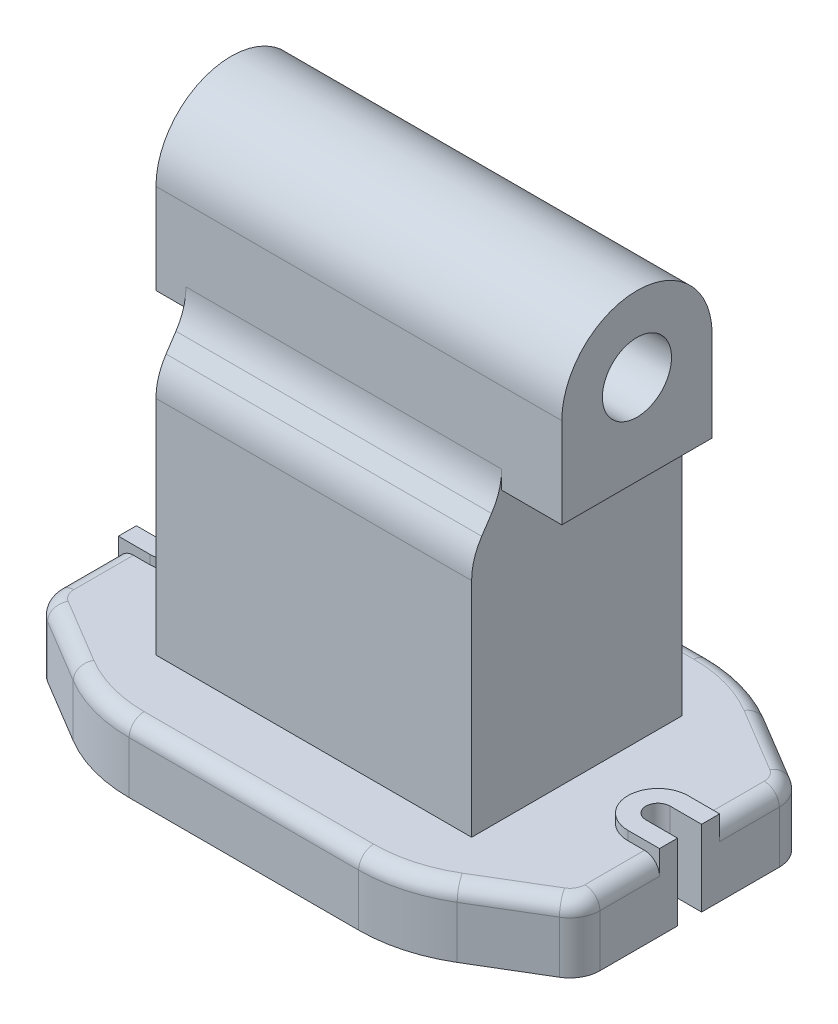
SolidWorks part; units mm, degrees
ref_plane "Front Plane" through (0, 0, 0) normal (0, 0, 1) x (1, 0, 0)
ref_plane "Top Plane" through (0, 0, 0) normal (0, 1, 0) x (1, 0, 0)
ref_plane "Right Plane" through (0, 0, 0) normal (1, 0, 0) x (0, 0, -1)
sketch "Sketch1" plane through (0, 0, 0) normal (0, 1, 0) x (1, 0, 0)
  line L0 (-27.5, 54.25) -> (-38, 54.25)
  line L1 (0, 0) -> (104, 0)
  line L3 (0, 116.5) -> (104, 116.5)
  line L5 (-38, 22.75) -> (0, 0)
  line L6 (-38, 54.25) -> (-38, 22.75)
  line L7 (-27.5, 62.25) -> (-38, 62.25)
  line L8 (-38, 62.25) -> (-38, 93.75)
  line L9 (-38, 93.75) -> (0, 116.5)
  line L10 (-38, 54.25) -> (-38, 62.25) construction
  line L11 (-38, 58.25) -> (142, 58.25) construction
  line L12 (52, 116.5) -> (52, 0) construction
  line L13 (142, 54.25) -> (142, 22.75)
  line L14 (142, 22.75) -> (104, 0)
  line L15 (131.5, 54.25) -> (142, 54.25)
  line L16 (131.5, 62.25) -> (142, 62.25)
  line L17 (142, 62.25) -> (142, 93.75)
  line L18 (142, 93.75) -> (104, 116.5)
  line L19 (142, 54.25) -> (142, 62.25) construction
  arc A0 (-27.5, 54.25) -> (-27.5, 62.25) centre (-27.5, 58.25) ccw
  arc A1 (131.5, 54.25) -> (131.5, 62.25) centre (131.5, 58.25) cw
  point P23 (144.2285, 58.25)
  point P24 (142, 58.25)
  dimension "D3" = 4
  dimension "D1" = 71
  dimension "D2" = 116.5
  dimension "D4" = 180
  dimension "D5" = 104
  dimension "D6" = 10.5
extrude "Base" add sketch "Sketch1" along normal blind 22.3
sketch "Sketch3" plane through (0, 22.3, 0) normal (0, 1, 0) x (1, 0, 0)
  line L0 (-27.5, 54.25) -> (-38, 54.25) construction
  line L1 (-38, 62.25) -> (-27.5, 62.25) construction
  line L2 (-27.5, 54.25) -> (-38, 54.25)
  line L3 (-38, 62.25) -> (-27.5, 62.25)
  line L8 (52, 0) -> (52, 116.5) construction
  line L9 (0, 0) -> (104, 0) construction
  line L10 (104, 116.5) -> (0, 116.5) construction
  line L11 (-38, 68.25) -> (-27.5, 68.25)
  line L12 (-27.5, 48.25) -> (-38, 48.25)
  line L13 (-38, 68.25) -> (-38, 62.25)
  line L14 (-38, 54.25) -> (-38, 48.25)
  line L15 (142, 54.25) -> (142, 48.25)
  line L16 (142, 68.25) -> (142, 62.25)
  line L17 (131.5, 48.25) -> (142, 48.25)
  line L18 (142, 68.25) -> (131.5, 68.25)
  line L19 (142, 62.25) -> (131.5, 62.25)
  line L20 (131.5, 54.25) -> (142, 54.25)
  arc A0 (-27.5, 54.25) -> (-27.5, 62.25) centre (-27.5, 58.25) ccw construction
  arc A1 (-27.5, 54.25) -> (-27.5, 62.25) centre (-27.5, 58.25) ccw
  arc A3 (-27.5, 48.25) -> (-27.5, 68.25) centre (-27.5, 58.25) ccw
  arc A4 (131.5, 48.25) -> (131.5, 68.25) centre (131.5, 58.25) cw
  arc A5 (131.5, 54.25) -> (131.5, 62.25) centre (131.5, 58.25) cw
  dimension "D1" = 6
extrude "Resalto - Furos de Fixação" add sketch "Sketch3" along normal blind 3
sketch "Sketch4" plane through (0, 22.3, 0) normal (0, 1, 0) x (1, 0, 0)
  line L0 (52, 116.5) -> (52, 0) construction
  line L1 (104, 116.5) -> (0, 116.5) construction
  line L2 (0, 0) -> (104, 0) construction
  line L4 (-0.5, 23.25) -> (104.5, 23.25)
  line L5 (-0.5, 23.25) -> (-0.5, 93.25)
  line L6 (-0.5, 93.25) -> (104.5, 93.25)
  line L7 (104.5, 23.25) -> (104.5, 93.25)
  line L8 (-0.5, 23.25) -> (104.5, 93.25) construction
  line L9 (-0.5, 93.25) -> (104.5, 23.25) construction
  point P6 (52, 58.25)
  dimension "105" = 105
  dimension "D2" = 70
extrude "Corpo Retangular" add sketch "Sketch4" along normal blind 80
sketch "Sketch5" plane through (-0.5, 0, 0) normal (-1, 0, 0) x (0, 0, 1)
  line L0 (-58.25, 147.3) -> (-58.25, 25.3) construction
  line L1 (-33.25, 147.3) -> (-33.25, 117.3)
  line L2 (-54.25, 25.3) -> (-62.25, 25.3) construction
  line L3 (-93.25, 22.3) -> (-23.25, 22.3) construction
  line L4 (-83.25, 147.3) -> (-83.25, 117.3)
  line L5 (-83.25, 117.3) -> (-93.25, 102.3)
  line L6 (-33.25, 117.3) -> (-23.25, 102.3)
  line L7 (-93.25, 102.3) -> (-23.25, 102.3)
  line L8 (-83.25, 117.3) -> (-33.25, 117.3)
  circle A0 centre (-58.25, 147.3) radius 11.5
  arc A1 (-33.25, 147.3) -> (-83.25, 147.3) centre (-58.25, 147.3) ccw
  line M11 (-23.25, 102.3) -> (-93.25, 102.3)
  dimension "D2" = 50
  dimension "D3" = 23
  dimension "D1" = 125
  dimension "D4" = 30
extrude "Corpo Inclinado" add sketch "Sketch5" against normal blind 105 contours L0 L8 L5 L7 | L8 L0 L6 M11 region at (-0.5, 109.3833, -43.1111) region at (-0.5, 109.3833, -73.3889)
extrude "Corpo Arredondado - Back" add sketch "Sketch5<4>" along normal blind 10 separate body contours A0 L8 L1 A1 L4 region at (-0.5, 132.3, -33.9933)
sketch "Sketch5<4>" plane through (-0.5, 0, 0) normal (-1, 0, 0) x (0, 0, 1) same geometry as "Sketch5"
extrude "Corpo Arredondado - Front" add sketch "Sketch5<5>" against normal blind 125 contours A0 L8 L1 A1 L4 region at (-0.5, 132.3, -33.9933)
sketch "Sketch5<5>" plane through (-0.5, 0, 0) normal (-1, 0, 0) x (0, 0, 1) same geometry as "Sketch5"
sketch "Sketch9" plane through (0, 0, 0) normal (0, -1, 0) x (1, 0, 0)
  line L0 (127.5, -58.25) -> (-23.5, -58.25) construction
  line L1 (52, 0) -> (52, -116.5) construction
  line L2 (0, 0) -> (104, 0) construction
  line L3 (104, -116.5) -> (0, -116.5) construction
  arc A0 (131.5, -54.25) -> (131.5, -62.25) centre (131.5, -58.25) ccw construction
  arc A1 (-27.5, -62.25) -> (-27.5, -54.25) centre (-27.5, -58.25) ccw construction
  circle A2 centre (2.5, -58.25) radius 4
  circle A3 centre (101.5, -58.25) radius 4
  dimension "D1" = 8
  dimension "D2" = 99
  dimension "D3" = 49.5
extrude "Pinos Guia" add sketch "Sketch9" along normal blind 20
fillet "Raios 50mm" radius 50 4 edges at (0, 11.15, -116.5) (104, 11.15, -116.5) (0, 11.15, 0) (104, 11.15, 0)
fillet "Raios 20mm" radius 20 4 edges at (52, 102.3, -93.25) (52, 117.3, -83.25) (52, 117.3, -33.25) (52, 102.3, -23.25)
fillet "Raios 10mm" radius 10 4 edges at (-38, 11.15, -93.75) (-38, 11.15, -22.75) (142, 11.15, -93.75) (142, 11.15, -22.75)
fillet "Raios 5mm" radius 5 18 edges at (142, 22.3, -78.1659) (140.6996, 22.3, -93.0129) (126.4984, 22.3, -103.0306) (103.5002, 22.3, -114.6922) (-38, 22.3, -78.1659) (-36.6996, 22.3, -93.0129) (-22.4984, 22.3, -103.0306) (0.4998, 22.3, -114.6922) (-38, 22.3, -38.3341) (-36.6996, 22.3, -23.4871) (-22.4984, 22.3, -13.4694) (0.4998, 22.3, -1.8078) (142, 22.3, -38.3341) (140.6996, 22.3, -23.4871) (126.4984, 22.3, -13.4694) (103.5002, 22.3, -1.8078) (52, 22.3, -116.5) (52, 22.3, 0)
sketch "Posição do Furo M10" plane through (-0.5, 0, 0) normal (-1, 0, 0) x (0, 0, 1)
  line L0 (-58.25, 158.8) -> (-58.25, 25.3) construction
  line L1 (-54.25, 25.3) -> (-62.25, 25.3) construction
  circle A0 centre (-58.25, 147.3) radius 11.5 construction
  circle A1 centre (-58.25, 97.3) radius 5
  dimension "D1" = 50
  dimension "D2" = 10
hole_wizard "Furo M10x50" positions "Sketch7" profile "Sketch8" tap size "M10x1.0" standard "ANSI Metric"
sketch "Sketch7" plane through (-0.5, 0, 0) normal (-1, 0, 0) x (0, 0, 1)
  point P0 (-58.25, 97.3)
sketch "Sketch8" plane through (-0.5, 97.3, -58.25) normal (0, 1, 0) x (0, 0, 1)
  line L0 (0, 0) -> (0, 50)
  line L1 (0, 50) -> (4.5, 47.2961)
  line L2 (4.5, 47.2961) -> (4.5, 0)
  line L5 (4.5, 0) -> (0, 0)
  line L10 (0, 50) -> (-4.5, 47.2961) construction
  line L11 (0, -6.35) -> (0, 107.95) construction
  dimension "Tap Drill Dia." = 9
  dimension "Tap Drill Depth" = 50
  dimension "Drill Angle" = 118
cosmetic thread "Hole Thread1" parameters "D1"=20, "D2"=10
